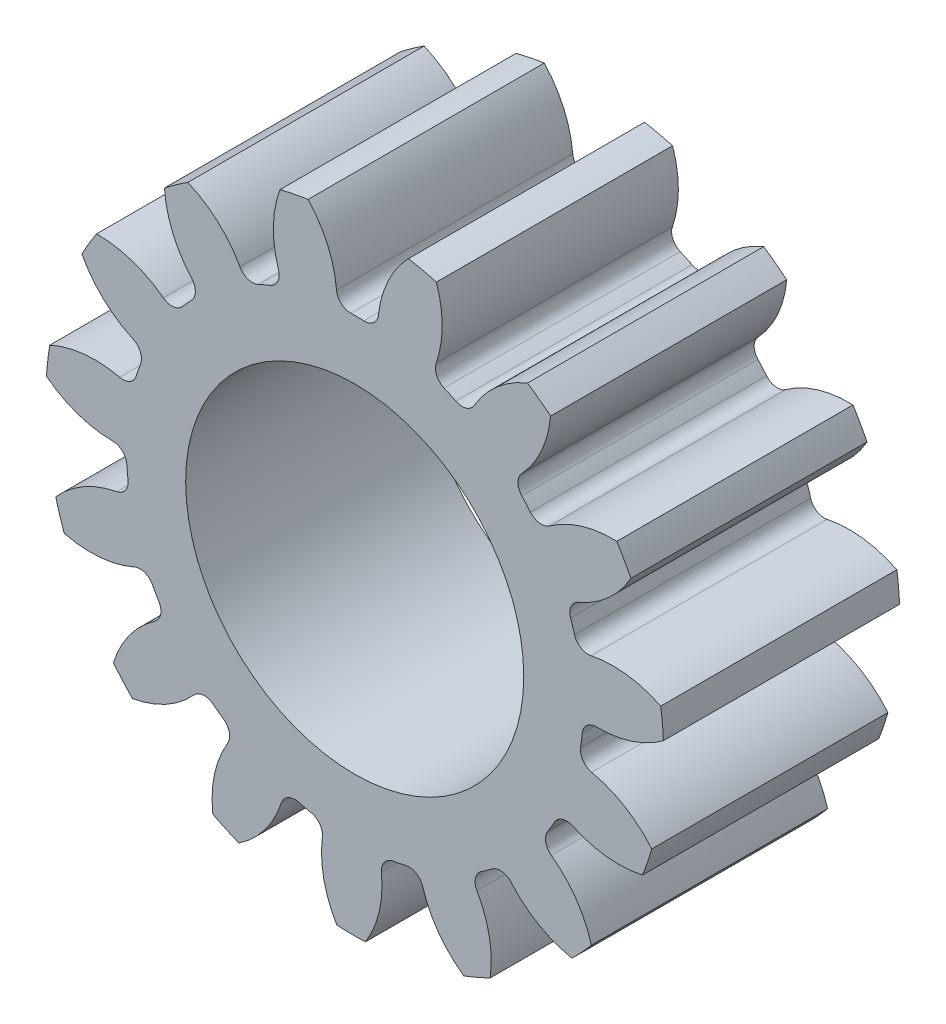
SolidWorks part; units mm, degrees
material "ABS"
ref_plane "Front" through (0, 0, 0) normal (0, 0, 1) x (1, 0, 0)
ref_plane "Top" through (0, 0, 0) normal (0, 1, 0) x (1, 0, 0)
ref_plane "Right" through (0, 0, 0) normal (1, 0, 0) x (0, 0, -1)
sketch "Sketch3" plane through (0, 0, 0) normal (0, 0, 1) x (1, 0, 0)
  circle A0 centre (0, 0) radius 21.59
  dimension "od" = 43.18
extrude "gearBody" add sketch "Sketch3" along normal blind 11
sketch "Sketch2" plane through (0, 0, 0) normal (0, 0, 1) x (1, 0, 0)
  line L0 (0, 0) -> (17.0393, 7.0579) construction
  line L1 (22.0105, -8.0941) -> (0, 0) construction
  line L2 (0, 0) -> (36.3143, 0) construction
  line L3 (19.0486, -0.229) -> (18.5878, -4.1711) construction
  line L5 (18.8182, -2.2) -> (0, 0) construction
  line L7 (0, 0) -> (18.4432, 0) construction
  arc A0 (18.4395, -0.3701) -> (18.0276, -3.8932) centre (0, 0) ccw construction
  arc A1 (21.5666, 1.0048) -> (20.7532, -5.9524) centre (0, 0) ccw construction
  arc A2 (19.0486, -0.229) -> (18.5878, -4.1711) centre (0, 0) ccw construction
  arc A3 (15.7838, -2.3046) -> (15.8898, -1.3984) centre (0, 0) ccw
  arc A4 (22.0105, -8.0941) -> (16.5506, -3.4102) centre (14.9518, -10.798) ccw
  arc A5 (22.0105, -8.0941) -> (23.2839, 2.7987) centre (0, 0) ccw
  arc A6 (23.2839, 2.7987) -> (16.8909, -0.4995) centre (17.0393, 7.0579) cw
  arc A7 (15.8898, -1.3984) -> (16.8909, -0.4995) centre (16.8715, -1.4848) cw
  arc A8 (16.5506, -3.4102) -> (15.7838, -2.3046) centre (16.759, -2.4469) cw
  point P6 (23.2839, 2.7987)
  point P22 (22.0105, -8.0941)
  dimension "baseDia" = 36.8864
  dimension "od" = 43.18
  dimension "pd" = 38.1
  dimension "rd" = 31.9024
  dimension "rFillet" = 0.9855
  dimension "pointX" = 23.2839
  dimension "pointY" = 2.7987
  dimension "CTT" = 3.9421
  dimension "flankCenterAngle" = 22.5
extrude "toothCut" cut sketch "Sketch2" along normal through all
pattern_circular "CirPattern1" count 15 over 360 about axis through (0, 0, 11) along (0, 0, -1) of "toothCut"
scale "Scale1" scale about centroid uniform scaling no x scale factor 0.666667 y scale factor 0.666667 z scale factor 1
sketch "hub1Dia" plane through (0, 0, 0) normal (0, 0, -1) x (-1, 0, 0)
  circle A0 centre (0, 0) radius 12.7
  dimension "hub1Dia" = 25.4
sketch "hub2Dia" plane through (0, 0, 11) normal (0, 0, 1) x (1, 0, 0)
  circle A0 centre (0, 0) radius 12.7
  dimension "hub2dia" = 25.4
sketch "boreDia" plane through (0, 0, 0) normal (0, 0, 1) x (1, 0, 0)
  circle A0 centre (0, 0) radius 7.874
  dimension "boreDia" = 15.748
extrude "bore" cut sketch "boreDia" against normal mid plane 25400
